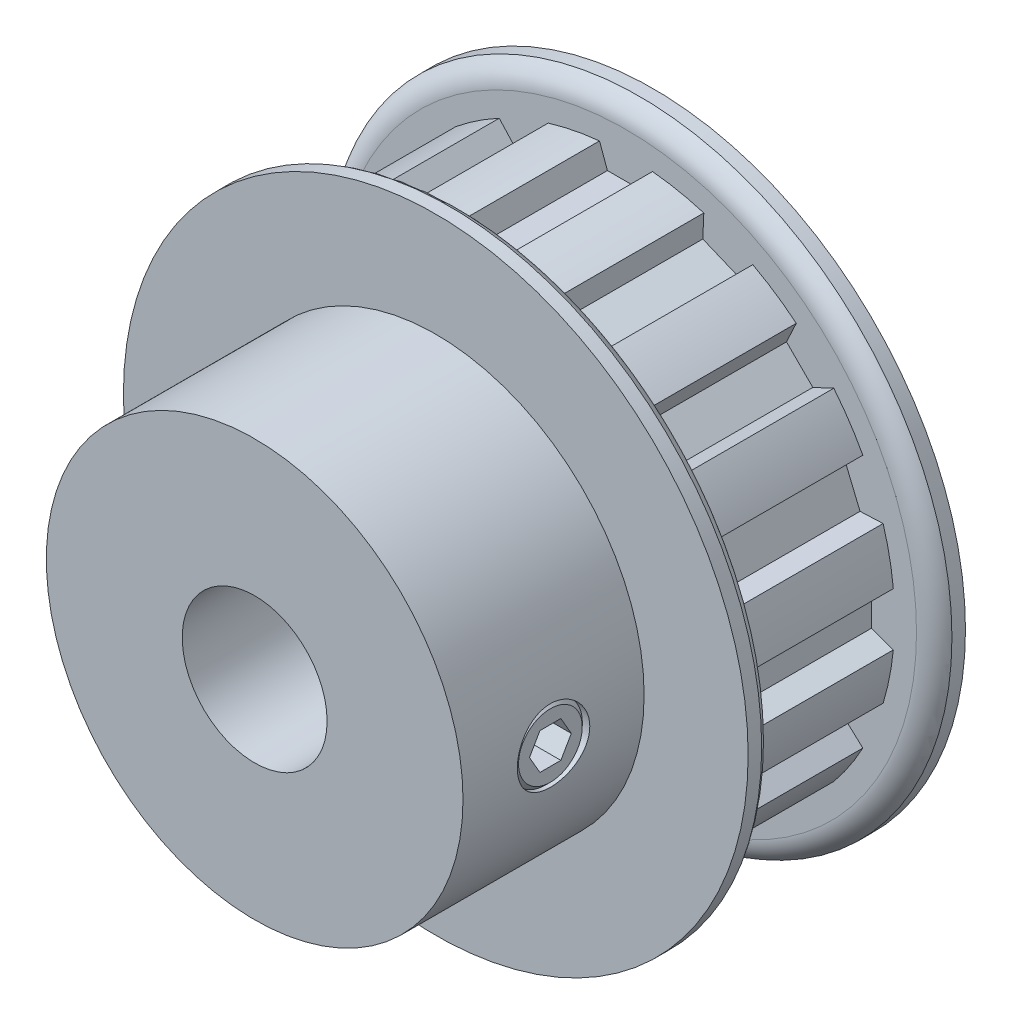
SolidWorks part; units mm, degrees
ref_plane "Front Plane" through (0, 0, 0) normal (0, 0, 1) x (1, 0, 0)
ref_plane "Top Plane" through (0, 0, 0) normal (0, 1, 0) x (1, 0, 0)
ref_plane "Right Plane" through (0, 0, 0) normal (1, 0, 0) x (0, 0, -1)
sketch "Sketch1" plane through (0, 0, 0) normal (0, 0, 1) x (1, 0, 0)
  line L0 (-2.3241, 23.4315) -> (-1.6307, 21.5265)
  line L1 (-1.6307, 21.5265) -> (1.6307, 21.5265)
  line L2 (1.6307, 21.5265) -> (2.3241, 23.4315)
  line L3 (-2.3241, 23.4315) -> (2.3241, 23.4315)
  line L4 (0, 0) -> (0, 21.5265) construction
  line L5 (0, 21.5265) -> (0, 25.0825) construction
  circle A0 centre (0, 0) radius 24.257 construction
  circle A1 centre (0, 0) radius 27.3812 construction
  circle A2 centre (0, 0) radius 23.5465 construction
  point P6 (0, 23.4315)
  point P11 (0, 24.257)
  point P13 (0, 27.3812)
  point P14 (0, 23.5465)
  dimension "D1" = 1.651
  dimension "D2" = 0.8255
sketch "Sketch2" plane through (0, 0, 0) normal (1, 0, 0) x (0, 0, -1)
  line L0 (-17.4625, 6.35) -> (17.4625, 6.35)
  line L1 (-17.4625, 6.35) -> (-17.4625, 18.2626)
  line L2 (-17.4625, 18.2626) -> (-1.5875, 18.2626)
  line L3 (-1.5875, 18.2626) -> (-1.5875, 27.3812)
  line L4 (-1.5875, 27.3812) -> (0.7874, 27.3812) construction
  line L5 (0.7874, 27.3812) -> (0.7874, 23.5465) construction
  line L6 (0.7874, 23.5465) -> (15.0876, 23.5465)
  line L7 (15.0876, 23.5465) -> (15.0876, 27.3812) construction
  line L8 (15.0876, 27.3812) -> (17.4625, 27.3812) construction
  line L9 (17.4625, 27.3812) -> (17.4625, 6.35)
  line L10 (-17.4625, 0) -> (17.4625, 0) construction
  line L13 (-1.5875, 27.3812) -> (-0.4001, 27.3812)
  line L14 (0.7874, 25.4638) -> (0.7874, 23.5465)
  line L15 (15.0876, 23.5465) -> (15.0876, 25.4638)
  line L16 (16.2751, 27.3812) -> (17.4625, 27.3812)
  arc A0 (0.7874, 25.4638) -> (-0.4001, 27.3812) centre (-1.3543, 25.4638) ccw
  arc A1 (15.0876, 25.4638) -> (16.2751, 27.3812) centre (17.2293, 25.4638) cw
  point P12 (0.7874, 25.4638)
  point P14 (-0.4001, 27.3812)
  point P20 (15.0876, 25.4638)
  point P21 (16.2751, 27.3812)
  point P25 (15.0876, 0)
  point P26 (0.7874, 0)
  dimension "Bore" = 12.7
  dimension "Hub Dia" = 36.5252
  dimension "Outside Width" = 19.05
  dimension "Inside Width" = 14.3002
revolve "Revolve1" add sketch "Sketch2" angle 360 mid plane about L10
sketch "Sketch3" plane through (0, 0, 0) normal (0, 0, 1) x (1, 0, 0)
  line L0 (-1.6307, 21.5265) -> (1.6307, 21.5265) construction
  line L1 (1.6307, 21.5265) -> (2.3241, 23.4315) construction
  line L2 (-2.3241, 23.4315) -> (-1.6307, 21.5265) construction
  line L3 (-1.6307, 21.5265) -> (1.6307, 21.5265)
  line L4 (1.6307, 21.5265) -> (2.3241, 23.4315)
  line L5 (-2.3241, 23.4315) -> (-1.6307, 21.5265)
  circle A0 centre (0, 0) radius 23.5465 construction
  arc A1 (2.3241, 23.4315) -> (-2.3241, 23.4315) centre (0, 0) ccw
extrude "Cut-Extrude1" cut sketch "Sketch3" against normal up to vertex (15.0876 mm away) from vertex up to point (0, 23.5465, -15.0876) starting at point (0, 23.5465, -0.7874)
pattern_circular "CirPattern1" count 16 over 360 about axis through (0, 0, 17.4625) along (0, 0, 1) of "Cut-Extrude1"
sketch "Sketch4" plane through (0, 0, 0) normal (1, 0, 0) x (0, -1, 0)
  line L0 (0, -1.5875) -> (0, -17.4625) construction
  line L1 (-18.2626, -1.5875) -> (18.2626, -1.5875) construction
  line L2 (-18.2626, -17.4625) -> (18.2626, -17.4625) construction
  circle A0 centre (0, -9.525) radius 3.175
  dimension "D1" = 6.35
extrude "Cut-Extrude2" cut sketch "Sketch4" along normal through all
ref_plane "Plane1" through (0, 0, 9.525) normal (0, 0, 1) x (1, 0, 0)
sketch "Sketch5" plane through (0, 0, 9.525) normal (0, 0, 1) x (1, 0, 0)
  line L0 (0, 0.1664) -> (0, 18.2626) construction
  line L1 (6.35, -2.794) -> (6.35, 0)
  line L2 (6.731, -3.175) -> (17.6035, -3.175)
  line L3 (6.35, 0) -> (18.2626, 0) construction
  line L4 (6.35, 0) -> (17.9845, 0)
  line L5 (17.9845, 0) -> (17.9845, -2.794)
  line L6 (6.731, -3.175) -> (6.35, -2.794)
  line L7 (17.9845, -2.794) -> (17.6035, -3.175)
  circle A0 centre (0, 0) radius 18.2626 construction
  circle A1 centre (0, 0) radius 6.35 construction
  point P2 (6.35, -3.175)
  point P11 (17.9845, -3.175)
revolve "Revolve2" add sketch "Sketch5" angle 360 mid plane about L4
sketch "Sketch6" plane through (17.9845, 5.3841, 0) normal (-1, 0, 0) x (0, -1, 0)
  line L1 (5.3841, 11.3581) -> (3.7966, 10.4415)
  line L2 (3.7966, 10.4415) -> (3.7966, 8.6085)
  line L3 (3.7966, 8.6085) -> (5.3841, 7.6919)
  line L4 (5.3841, 7.6919) -> (6.9716, 8.6085)
  line L5 (6.9716, 8.6085) -> (6.9716, 10.4415)
  line L6 (6.9716, 10.4415) -> (5.3841, 11.3581)
  circle A0 centre (5.3841, 9.525) radius 1.5875 construction
  dimension "D1" = 3.175
extrude "Cut-Extrude3" cut sketch "Sketch6" along normal blind 2.3813
equation "\"D2@Sketch1\" = \"D1@Sketch1\"/2"
equation "\"D1@Sketch4\" = \"Bore@Sketch2\"/2"
equation "\"D1@Sketch6\" = \"D1@Sketch4\"/2"
equation "\"D1@Cut-Extrude3\" = \"D1@Sketch6\"*.75"
